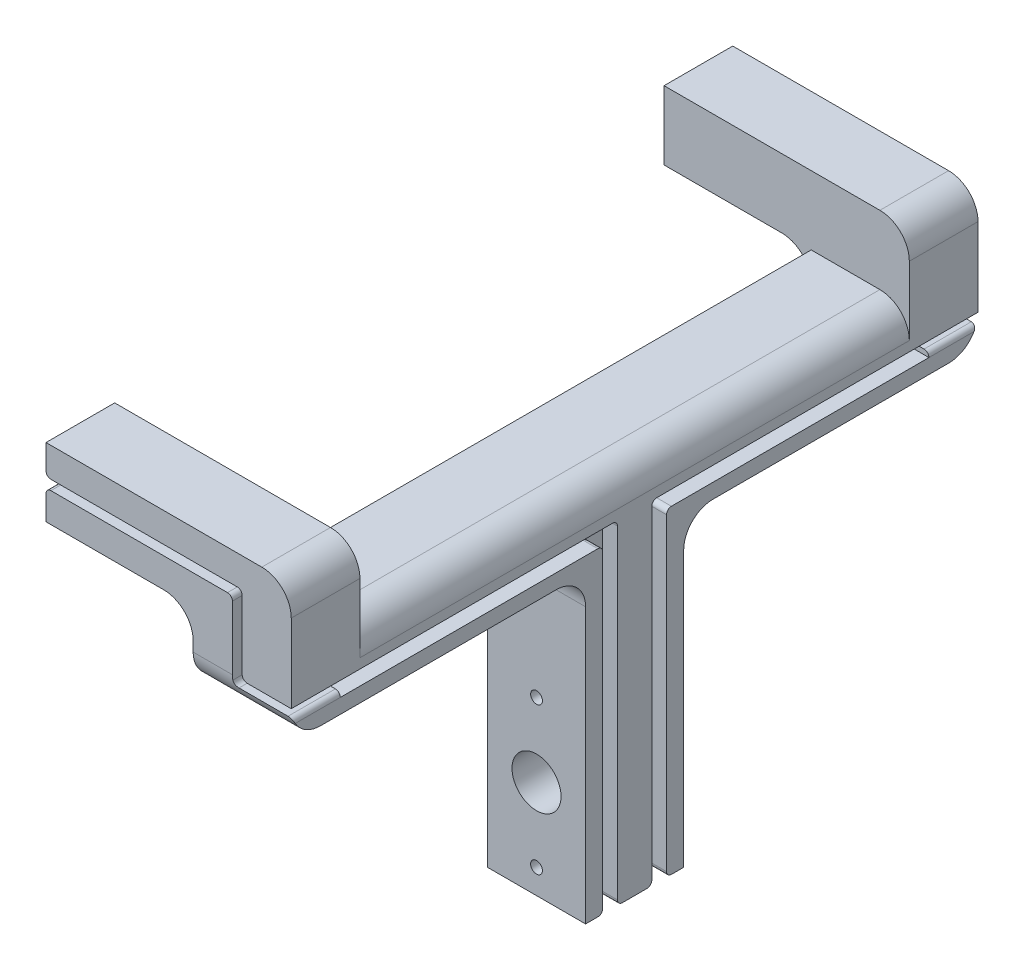
SolidWorks part; units mm, degrees
other "Marquage1"
sketch "Esquisse8" plane through (14, 100, 40) normal (0.0145, 0.0452, 0.9989) x (0.9993, 0.0332, -0.016)
ref_plane "Plan de face" through (0, 0, 0) normal (0, 0, 1) x (1, 0, 0)
ref_plane "Plan de dessus" through (0, 0, 0) normal (0, 1, 0) x (1, 0, 0)
ref_plane "Plan de droite" through (0, 0, 0) normal (1, 0, 0) x (0, 0, -1)
sketch "Esquisse1" plane through (0, 0, 0) normal (0, 0, 1) x (1, 0, 0)
  line L0 (9, 0) -> (9, 10) construction
  line L1 (0, 0) -> (18, 0) construction
  line L2 (0, 0) -> (0, 38) construction
  line L3 (0, 38) -> (18, 38) construction
  line L4 (18, 0) -> (18, 38) construction
  line L5 (9, 10) -> (0, 10) construction
  line L6 (9, 10) -> (9, 17.5) construction
  line L7 (4, 38) -> (14, 38)
  line L8 (4, 38) -> (4, 0)
  line L10 (14, 38) -> (14, 0)
  line L11 (4, 0) -> (14, 0)
  circle A1 centre (9, 10) radius 2.5
  circle A2 centre (9, 17.5) radius 0.5
  circle A4 centre (9, 2.5) radius 0.5
  circle A6 centre (16.5, 10) radius 0.5 [skipped]
  circle A7 centre (1.5, 10) radius 0.5 [skipped]
  point P24 (9, 10)
  dimension "D7" = 5
  dimension "D9" = 1
  dimension "D1" = 18
  dimension "D2" = 38
  dimension "D3" = 10
  dimension "D5" = 10
  dimension "D6" = 4
  dimension "D8" = 7.5
  dimension "D4" = 7.5
  dimension "D10" = 4
extrude "Boss.-Extru.1" add sketch "Esquisse1" along normal blind 10
sketch "Esquisse4" plane through (14, 0, 0) normal (1, 0, 0) x (0, 0, -1)
  line L0 (-33, 38) -> (23, 38)
  line L1 (23, 45) -> (30, 45)
  line L2 (30, 45) -> (30, 31)
  line L3 (30, 31) -> (-40, 31)
  line L4 (-40, 31) -> (-40, 45)
  line L5 (-40, 45) -> (-33, 45)
  line L6 (-33, 45) -> (-33, 38)
  line L8 (23, 38) -> (23, 45)
  line L9 (-5, 38) -> (-5, 0) construction
  line L10 (-10, 38) -> (0, 38) construction
  line L11 (-10, 0) -> (0, 0) construction
  point P5 (-5, 38)
  point P15 (-5, 31)
  dimension "D1" = 70
  dimension "D2" = 7
  dimension "D3" = 7
  dimension "D4" = 45
  dimension "D5" = 45
extrude "Boss.-Extru.2" add sketch "Esquisse4" against normal blind 10
sketch "Esquisse5" plane through (4, 0, 0) normal (-1, 0, 0) x (0, 0, 1)
  line L0 (-23, 45) -> (-23, 38) construction
  line L1 (-30, 45) -> (-23, 45)
  line L2 (-30, 45) -> (-30, 38)
  line L3 (-30, 38) -> (-23, 38)
  line L4 (-23, 45) -> (-23, 38)
  line L5 (40, 45) -> (40, 31) construction
  line L6 (33, 45) -> (40, 45)
  line L7 (33, 45) -> (33, 38)
  line L8 (33, 38) -> (40, 38)
  line L9 (40, 45) -> (40, 38)
  point P14 (-23, 38)
extrude "Boss.-Extru.3" add sketch "Esquisse5" along normal blind 15
fillet "Congé1" radius 3 9 edges at (4, 38, -26.5) (4, 38, 36.5) (9, 31, -30) (9, 31, 40) (14, 45, -26.5) (14, 45, 36.5) (9, 31, 0) (9, 31, 10) (14, 38, 5)
hole_wizard "Dégagement M11" positions "Esquisse6" profile "Esquisse7" hole size "M1" standard "ISO" end condition through all
sketch "Esquisse6" plane through (0, 0, 10) normal (0, 0, 1) x (1, 0, 0)
  point P0 (9, 17.5)
  point P3 (9, 2.5)
sketch "Esquisse7" plane through (9, 17.5, 10) normal (1, 0, 0) x (0, -1, 0)
  line L0 (0, 0) -> (0, 40)
  line L1 (0, 40) -> (0.6, 40)
  line L2 (0.6, 40) -> (0.6, 0)
  line L5 (0.6, 0) -> (0, 0)
  line L11 (0, -6.35) -> (0, 107.95) construction
  dimension "Diamètre du perçage jusqu'au prochain" = 1.2
  dimension "Profondeur du perçage jusqu'au prochain" = 40
sketch "Esquisse9" plane through (14, 0, 0) normal (1, 0, 0) x (0, 0, -1)
  line L5 (0, 0) -> (-2.5, 0)
  line L6 (0, 0) -> (0, 20)
  line L7 (0, 20) -> (-2.5, 20)
  line L8 (-2.5, 0) -> (-2.5, 20)
  dimension "D2" = 20
  dimension "D4" = 2.5
extrude "Enlèv. mat.-Extru.1" [suppressed] cut sketch "Esquisse9" against normal up to surface (10 mm away) up to face at (4, 29, 5)
sketch "Esquisse10" plane through (0, 0, 40) normal (0, 0, 1) x (1, 0, 0)
  line L0 (-11, 38) -> (-11, 45) construction
  line L1 (-11, 41) -> (8, 41)
  line L2 (-11, 41) -> (-11, 42)
  line L3 (-11, 42) -> (9, 42)
  line L7 (9, 42) -> (9, 34)
  line L9 (8, 41) -> (8, 33)
  line L10 (8, 33) -> (14, 33)
  line L12 (9, 34) -> (14, 34)
  line L13 (14, 33) -> (14, 34)
  point P3 (8.4216, 33)
  point P7 (8.7934, 42.3541)
  point P9 (13.9497, 33.2539)
  point P13 (14, 34)
  point P15 (14, 32.585)
  point P16 (-11, 41.5)
  point P17 (-11, 41.5)
  point P18 (7.494, 33.3491)
  dimension "D1" = 1
  dimension "D2" = 1
  dimension "D3" = 1
  dimension "D4" = 20
extrude "Enlèv. mat.-Extru.2" cut sketch "Esquisse10" against normal blind 5
ref_plane "Plan1" through (0, 0, 5) normal (0, 0, 1) x (1, 0, 0)
sketch "Esquisse11" plane through (14, 0, 0) normal (1, 0, 0) x (0, 0, -1)
  line L0 (-10, 0) -> (0, 0) construction
  line L1 (-35, 34) -> (-6.75, 34)
  line L2 (-35, 34) -> (-35, 32.5)
  line L3 (-35, 32.5) -> (-8.25, 32.5)
  line L6 (-6.75, 34) -> (-6.75, 0)
  line L7 (-6.75, 0) -> (-8.25, 0)
  line L8 (-8.25, 32.5) -> (-8.25, 0)
  line L9 (-10, 0) -> (-10, 28) construction
  point P8 (-8.3633, 0)
  point P11 (-7.5, 0)
  point P14 (-6.75, 33.8892)
  dimension "D1" = 1.5
  dimension "D2" = 2.5
  dimension "D3" = 1.5
extrude "Enlèv. mat.-Extru.3" cut sketch "Esquisse11" against normal blind 1.5
mirror "Symétrie1" about plane through (0, 0, 5) normal (0, 0, 1) of "Enlèv. mat.-Extru.3", "Enlèv. mat.-Extru.2"
fillet "Congé2" radius 0.5 26 edges at (13.25, 0, 8.25) (12.5, 0, 7.5) (13.25, 0, 6.75) (13.25, 34, 6.75) (13.25, 32.5, 8.25) (-11, 41, 37.5) (-11, 42, 37.5) (14, 33, 37.4142) (8, 33, 37.4142) (9, 34, 37.5) (9, 42, 37.5) (8, 41, 37.5) (-11, 41.5, 35) (-11, 41, -27.5) (-11, 41.5, -25) (-11, 42, -27.5) (9, 42, -27.5) (8, 41, -27.5) (8, 33, -27.4142) (9, 34, -27.5) (14, 33, -27.4142) (13.25, 0, 1.75) (13.25, 0, 3.25) (12.5, 0, 2.5) (13.25, 32.5, 1.75) (13.25, 34, 3.25)
equation "\"D3@Esquisse1\"=10"
equation "\"D6@Esquisse1\"=(\"D1@Esquisse1\"-\"D5@Esquisse1\")/2"
equation "\"D8@Esquisse1\"=15/2"
